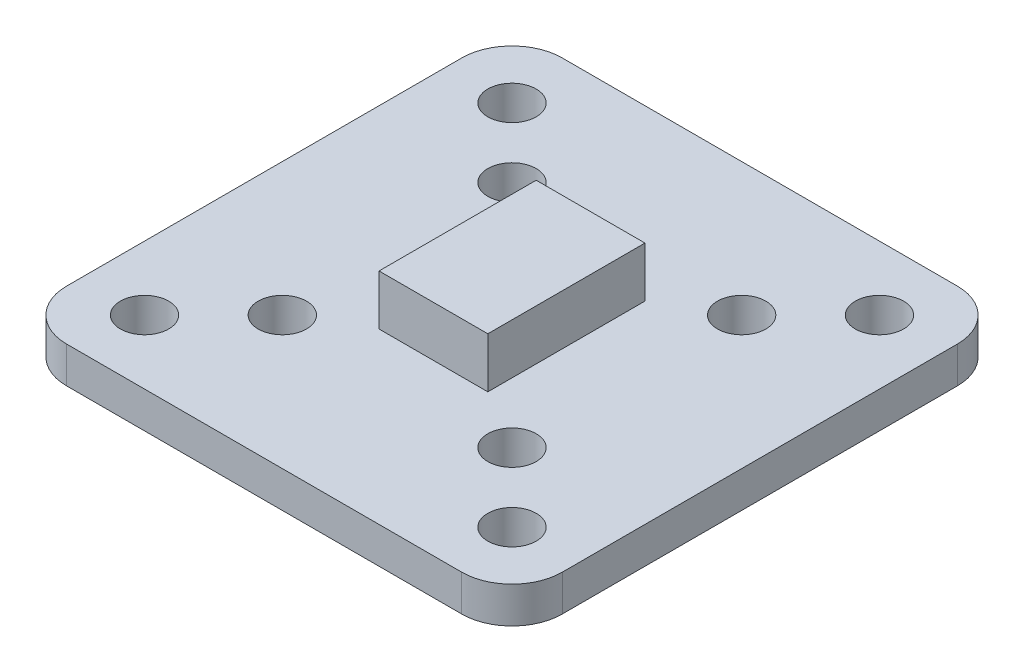
SolidWorks part; units mm, degrees
ref_plane "Front Plane" through (0, 0, 0) normal (0, 0, 1) x (1, 0, 0)
ref_plane "Top Plane" through (0, 0, 0) normal (0, 1, 0) x (1, 0, 0)
ref_plane "Right Plane" through (0, 0, 0) normal (1, 0, 0) x (0, 0, -1)
sketch "Sketch1" plane through (0, 0, 0) normal (0, 1, 0) x (1, 0, 0)
  line L0 (-16.2719, 0) -> (16.2719, 0) construction
  line L1 (12.9699, -16.2719) -> (-12.9699, -16.2719)
  line L2 (16.2719, -12.9699) -> (16.2719, 12.9699)
  line L3 (12.9699, 16.2719) -> (-12.9699, 16.2719)
  line L4 (-16.2719, -12.9699) -> (-16.2719, 12.9699)
  line L5 (16.2719, -16.2719) -> (-16.2719, 16.2719) construction
  line L6 (16.2719, 16.2719) -> (-16.2719, -16.2719) construction
  line L7 (3.5719, -5.1594) -> (-3.5719, -5.1594)
  line L8 (3.5719, -5.1594) -> (3.5719, 5.1594)
  line L9 (3.5719, 5.1594) -> (-3.5719, 5.1594)
  line L10 (-3.5719, -5.1594) -> (-3.5719, 5.1594)
  line L11 (3.5719, -5.1594) -> (-3.5719, 5.1594) construction
  line L12 (3.5719, 5.1594) -> (-3.5719, -5.1594) construction
  line L13 (-5.5562, 5.5562) -> (5.5562, 5.5562)
  line L14 (-5.5562, 5.5562) -> (-5.5562, -5.5562)
  line L15 (-5.5562, -5.5562) -> (5.5562, -5.5562)
  line L16 (5.5562, 5.5562) -> (5.5562, -5.5562)
  line L17 (-5.5562, 5.5562) -> (5.5562, -5.5562) construction
  line L18 (-5.5562, -5.5562) -> (5.5562, 5.5562) construction
  circle A0 centre (12.065, 12.065) radius 1.5875
  circle A1 centre (7.5406, 7.5406) radius 1.5875
  circle A2 centre (-7.5406, -7.5406) radius 1.5875
  circle A3 centre (-12.065, -12.065) radius 1.5875
  circle A4 centre (-12.065, 12.065) radius 1.5875
  circle A5 centre (-7.5406, 7.5406) radius 1.5875
  circle A6 centre (7.5406, -7.5406) radius 1.5875
  circle A7 centre (12.065, -12.065) radius 1.5875
  arc A8 (16.2719, -12.9699) -> (12.9699, -16.2719) centre (12.9699, -12.9699) cw
  arc A9 (-12.9699, -16.2719) -> (-16.2719, -12.9699) centre (-12.9699, -12.9699) cw
  arc A10 (16.2719, 12.9699) -> (12.9699, 16.2719) centre (12.9699, 12.9699) ccw
  arc A11 (-12.9699, 16.2719) -> (-16.2719, 12.9699) centre (-12.9699, 12.9699) ccw
  point P0 (0, 0)
  point P10 (0, 0)
  point P15 (0, 0)
  dimension "D3" = 4.2069
  dimension "D4" = 3.175
  dimension "D5" = 3.175
  dimension "D6" = 8.7312
  dimension "D9" = 3.302
  dimension "D1" = 32.5437
  dimension "D2" = 32.5437
  dimension "D7" = 10.3187
  dimension "D8" = 7.1437
  dimension "D10" = 7.8577
extrude "Boss-Extrude1" add sketch "Sketch1" against normal blind 2.3813 contours L4 A11 L3 A10 L2 A8 L1 A9
extrude "Boss-Extrude2" add sketch "Sketch1<4>" along normal blind 3.302 contours L10 L9 L8 L7
sketch "Sketch1<4>" plane through (0, 0, 0) normal (0, 1, 0) x (1, 0, 0) same geometry as "Sketch1"
extrude "Cut-Extrude1" cut sketch "Sketch1<5>" against normal through all contours A4 | A2 | A6 | A7 | A0 | A5 | A3 | A1 region at (12.065, 0, -12.065) region at (-7.5406, 0, 7.5406) region at (-12.065, 0, -12.065) region at (7.5406, 0, 7.5406) region at (12.065, 0, 12.065)
sketch "Sketch1<5>" plane through (0, 0, 0) normal (0, 1, 0) x (1, 0, 0) same geometry as "Sketch1"
